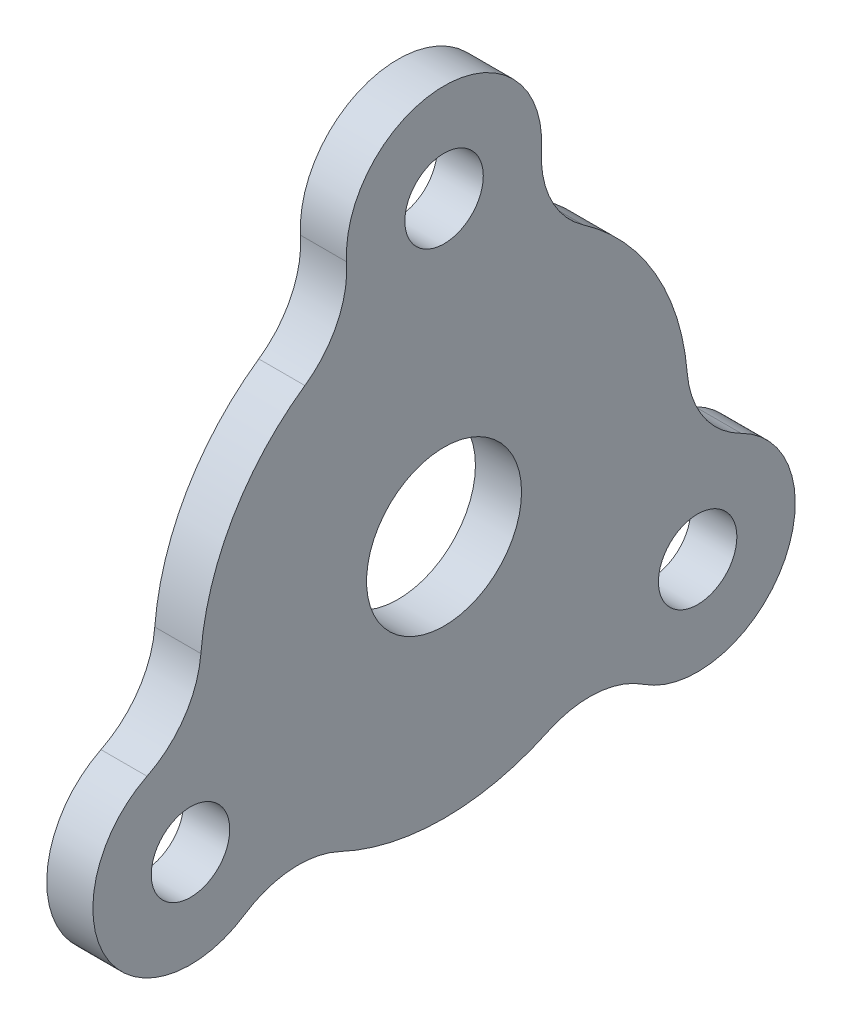
SolidWorks part; units mm, degrees
material "AR500"
ref_plane "Front Plane" through (0, 0, 0) normal (0, 0, 1) x (1, 0, 0)
ref_plane "Top Plane" through (0, 0, 0) normal (0, 1, 0) x (1, 0, 0)
ref_plane "Right Plane" through (0, 0, 0) normal (1, 0, 0) x (0, 0, -1)
sketch "Sketch1" plane through (0, 0, 0) normal (1, 0, 0) x (0, 0, -1)
  line L1 (0, 19.05) -> (-16.4978, -9.525) construction
  line L2 (-16.4978, -9.525) -> (16.4978, -9.525) construction
  line L3 (16.4978, -9.525) -> (0, 19.05) construction
  arc A1 (-9.0537, 13.0402) -> (-15.82, 1.3206) centre (0, 0) ccw
  circle A2 centre (0, 19.05) radius 2.5527
  circle A3 centre (-16.4978, -9.525) radius 2.5527
  circle A4 centre (16.4978, -9.525) radius 2.5527
  arc A6 (-15.82, 1.3206) -> (-19.3229, -3.8381) centre (-22.148, 1.8489) cw
  arc A7 (-19.3229, -3.8381) -> (-12.9853, -14.8151) centre (-16.4978, -9.525) ccw
  arc A8 (-12.9853, -14.8151) -> (-6.7663, -14.3608) centre (-9.4728, -20.1051) cw
  circle A9 centre (0, 0) radius 19.05 construction
  arc A10 (9.0537, 13.0402) -> (6.3376, 18.6531) centre (12.6752, 18.2563) cw
  arc A11 (6.3376, 18.6531) -> (-6.3376, 18.6531) centre (0, 19.05) ccw
  arc A12 (-6.3376, 18.6531) -> (-9.0537, 13.0402) centre (-12.6752, 18.2563) cw
  arc A13 (6.7663, -14.3608) -> (12.9853, -14.8151) centre (9.4728, -20.1051) cw
  arc A14 (12.9853, -14.8151) -> (19.3229, -3.8381) centre (16.4978, -9.525) ccw
  arc A15 (19.3229, -3.8381) -> (15.82, 1.3206) centre (22.148, 1.8489) cw
  circle A16 centre (0, 19.05) radius 2.5527 construction
  arc A17 (15.82, 1.3206) -> (9.0537, 13.0402) centre (0, 0) ccw
  arc A19 (-6.7663, -14.3608) -> (6.7663, -14.3608) centre (0, 0) ccw
  point P35 (0, 0)
  dimension "D4" = 5.1054
  dimension "D5" = 6.35
  dimension "D6" = 6.35
  dimension "D7" = 15.875
  dimension "D2" = 3
extrude "Boss-Extrude1" add sketch "Sketch1" along normal blind 3
sketch "Sketch5" plane through (3, 0, 0) normal (1, 0, 0) x (0, 0, -1)
  point P0 (0, 0)
hole_wizard "3/8 Clearance Hole1" positions "Sketch5" profile "Sketch6" hole size "3/8" standard "ANSI Inch" end condition through all
sketch "Sketch6" plane through (3, 0, 0) normal (0, 1, 0) x (0, 0, -1)
  line L0 (0, 0) -> (0, 3)
  line L1 (0, 3) -> (5.0419, 3)
  line L2 (5.0419, 3) -> (5.0419, 0)
  line L5 (5.0419, 0) -> (0, 0)
  line L11 (0, -6.35) -> (0, 107.95) construction
  dimension "Thru Hole Dia." = 10.0838
  dimension "Thru Hole Depth" = 3
